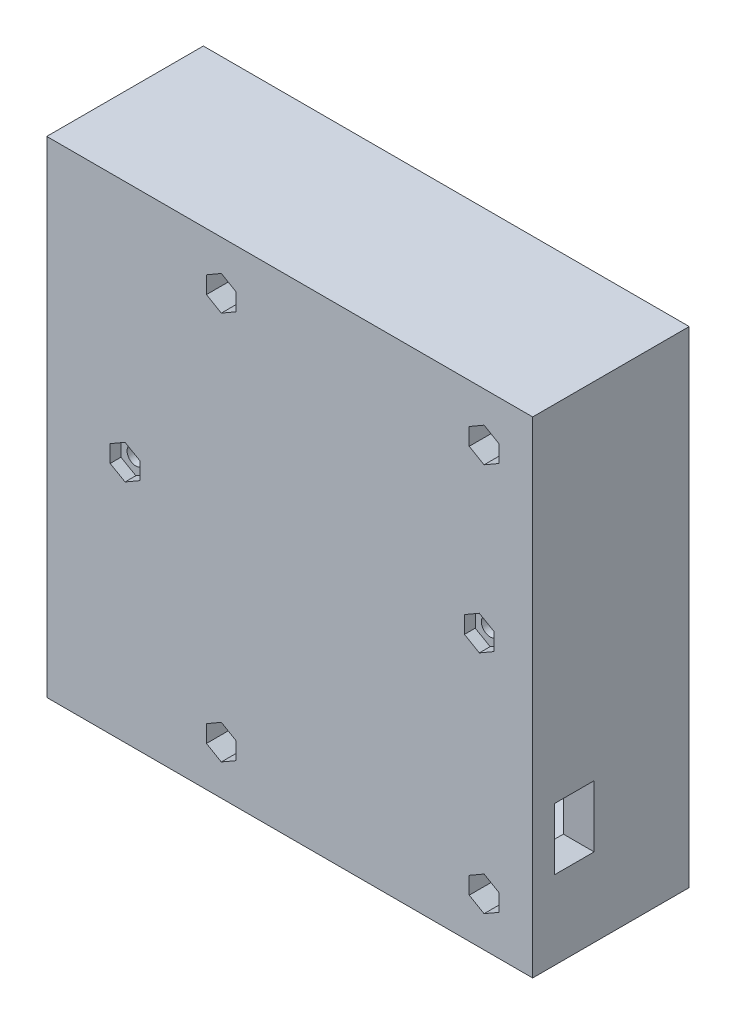
SolidWorks part; units mm, degrees
ref_plane "Alzado" through (0, 0, 0) normal (0, 0, 1) x (1, 0, 0)
ref_plane "Planta" through (0, 0, 0) normal (0, 1, 0) x (1, 0, 0)
ref_plane "Vista lateral" through (0, 0, 0) normal (1, 0, 0) x (0, 0, -1)
sketch "Croquis1" plane through (0, 0, 0) normal (0, 0, 1) x (1, 0, 0)
  line L0 (-44.4885, -46.7117) -> (45.5115, -46.7117)
  line L1 (45.5115, -46.7117) -> (45.5115, 43.2883)
  line L2 (34.2095, -31.6555) -> (34.2095, -33.0328) construction
  line L4 (-43.9885, 43.2883) -> (-45.9617, 43.2883) construction
  line L5 (-44.4885, 42.7883) -> (-44.4885, 44.5722) construction
  line L6 (-44.4885, 43.2883) -> (-44.4885, -46.7117)
  line L7 (-44.4885, 43.2883) -> (45.5115, 43.2883)
  dimension "D1" = 34.2095
  dimension "D2" = 45.5115
extrude "Saliente-Extruir1" add sketch "Croquis1" along normal blind 4
sketch "Croquis2" plane through (0, 0, 0) normal (0, 0, -1) x (-1, 0, 0)
  line L0 (-19.2301, 43.2883) -> (-19.2301, 39.2883) construction
  line L1 (-45.5115, 43.2883) -> (44.4885, 43.2883) construction
  line L2 (-45.5115, 28.7784) -> (-41.5115, 28.7784) construction
  line L3 (-45.5115, -46.7117) -> (-45.5115, 43.2883) construction
  line L4 (-24.9283, -46.7117) -> (-24.9283, -42.7117) construction
  line L5 (44.4885, -46.7117) -> (-45.5115, -46.7117) construction
  line L6 (44.4885, -27.1574) -> (40.4885, -27.1574) construction
  line L7 (44.4885, 43.2883) -> (44.4885, -46.7117) construction
  line L8 (40.4885, -27.1574) -> (40.4885, -42.7117)
  line L9 (40.4885, -42.7117) -> (-41.5115, -42.7117)
  line L10 (-41.5115, -42.7117) -> (-41.5115, 39.2883)
  line L11 (-41.5115, 39.2883) -> (40.4885, 39.2883)
  line L12 (40.4885, 39.2883) -> (40.4885, -27.1574)
  line L14 (-45.5115, 43.2883) -> (44.4885, 43.2883)
  line L15 (-45.5115, 43.2883) -> (-45.5115, -46.7117)
  line L16 (-45.5115, -46.7117) -> (44.4885, -46.7117)
  line L17 (44.4885, 43.2883) -> (44.4885, -46.7117)
  dimension "D1" = 4
  dimension "D2" = 20.5832
  dimension "D3" = 26.2813
  dimension "D4" = 19.5543
  dimension "D5" = 75.4901
extrude "Saliente-Extruir2" add sketch "Croquis2" along normal blind 25
sketch "Croquis4" plane through (45.5115, 0, 0) normal (1, 0, 0) x (0, 0, -1)
  line L0 (2.411, -26.4653) -> (-4, -26.4653) construction
  line L1 (0, -21.4747) -> (0, -31.4518)
  line L5 (0, -31.4518) -> (0, -32.1752)
  line L6 (0, -32.1752) -> (7.3834, -32.1752)
  line L13 (7.3834, -32.1752) -> (7.3834, -31.4518)
  line L14 (-4, -25.6688) -> (0, -25.6688) construction
  line L15 (7.3834, -21.4747) -> (7.3834, -20.7513)
  line L16 (7.3834, -21.4747) -> (7.3834, -31.4518)
  line L18 (7.3834, -20.7513) -> (0, -20.7513)
  line L19 (0, -20.7513) -> (0, -21.4747)
extrude "Cortar-Extruir1" cut sketch "Croquis4" against normal blind 4 draft 23
sketch "Croquis6" plane through (0, 0, 0) normal (0, 0, -1) x (-1, 0, 0)
  line L0 (-41.5115, 39.2883) -> (-41.5115, -42.7117) construction
  line L1 (-41.5115, 39.2883) -> (-31.5115, 39.2883)
  line L2 (-41.5115, 39.2883) -> (-41.5115, 29.2883)
  line L3 (-41.5115, 29.2883) -> (-31.5115, 29.2883)
  line L4 (-31.5115, 39.2883) -> (-31.5115, 29.2883)
  line L5 (40.4885, 39.2883) -> (-41.5115, 39.2883) construction
  line L6 (-41.5115, -42.7117) -> (40.4885, -42.7117) construction
  line L7 (-41.5115, -42.7117) -> (-31.5115, -42.7117)
  line L8 (-41.5115, -42.7117) -> (-41.5115, -32.7117)
  line L9 (-41.5115, -32.7117) -> (-31.5115, -32.7117)
  line L10 (-31.5115, -42.7117) -> (-31.5115, -32.7117)
  line L11 (-41.5115, 39.2883) -> (-41.5115, -42.7117) construction
  line L12 (40.4885, 39.2883) -> (-41.5115, 39.2883) construction
  line L14 (17.1571, -42.7117) -> (7.1571, -42.7117)
  line L15 (17.1571, -42.7117) -> (17.1571, -32.7117)
  line L16 (17.1571, -32.7117) -> (7.1571, -32.7117)
  line L17 (7.1571, -42.7117) -> (7.1571, -32.7117)
  line L18 (17.1571, 39.2883) -> (7.1571, 39.2883)
  line L19 (17.1571, 39.2883) -> (17.1571, 29.2883)
  line L20 (17.1571, 29.2883) -> (7.1571, 29.2883)
  line L21 (7.1571, 39.2883) -> (7.1571, 29.2883)
  dimension "D1" = 10
  dimension "D2" = 48.6686
extrude "Saliente-Extruir4" add sketch "Croquis6" along normal blind 4
sketch "Croquis7" plane through (0, 0, -4) normal (0, 0, -1) x (-1, 0, 0)
  line L0 (-36.5115, -32.7117) -> (-36.5115, -42.7117) construction
  line L1 (-31.5115, -32.7117) -> (-41.5115, -32.7117) construction
  line L2 (-41.5115, -42.7117) -> (40.4885, -42.7117) construction
  line L3 (-36.5115, 29.2883) -> (-36.5115, 39.2883) construction
  line L4 (-41.5115, 29.2883) -> (-31.5115, 29.2883) construction
  line L5 (40.4885, 39.2883) -> (-41.5115, 39.2883) construction
  line L6 (-31.5115, 34.2883) -> (-41.5115, 34.2883) construction
  line L7 (-31.5115, 29.2883) -> (-31.5115, 39.2883) construction
  line L8 (-41.5115, 39.2883) -> (-41.5115, -42.7117) construction
  line L9 (-31.5115, -37.7117) -> (-41.5115, -37.7117) construction
  line L10 (-31.5115, -42.7117) -> (-31.5115, -32.7117) construction
  line L12 (12.1571, -32.7117) -> (12.1571, -42.7117) construction
  line L13 (17.1571, -32.7117) -> (7.1571, -32.7117) construction
  line L14 (12.1571, 29.2883) -> (12.1571, 39.2883) construction
  line L15 (7.1571, 29.2883) -> (17.1571, 29.2883) construction
  line L16 (-41.5115, 39.2883) -> (-41.5115, 29.2883) construction
  circle A0 centre (-36.5115, 34.2883) radius 1.625
  circle A1 centre (-36.5115, -37.7117) radius 1.625
  circle A2 centre (12.1571, -37.7117) radius 1.625
  circle A3 centre (12.1571, 34.2883) radius 1.625
  dimension "D1" = 3.25
extrude "Cortar-Extruir2" cut sketch "Croquis7" against normal up to vertex (8 mm away) up to point (-44.4885, 43.2883, 4)
sketch "Croquis8" plane through (0, 0, 4) normal (0, 0, 1) x (1, 0, 0)
  line L0 (45.5115, -46.7117) -> (45.5115, 43.2883) construction
  line L1 (36.5115, -40.8917) -> (39.2654, -39.3017)
  line L2 (39.2654, -39.3017) -> (39.2654, -36.1217)
  line L3 (39.2654, -36.1217) -> (36.5115, -34.5317)
  line L4 (36.5115, -34.5317) -> (33.7575, -36.1217)
  line L5 (33.7575, -36.1217) -> (33.7575, -39.3017)
  line L6 (33.7575, -39.3017) -> (36.5115, -40.8917)
  line L7 (36.5115, 31.1083) -> (39.2654, 32.6983)
  line L8 (39.2654, 32.6983) -> (39.2654, 35.8783)
  line L9 (39.2654, 35.8783) -> (36.5115, 37.4683)
  line L10 (36.5115, 37.4683) -> (33.7575, 35.8783)
  line L11 (33.7575, 35.8783) -> (33.7575, 32.6983)
  line L12 (33.7575, 32.6983) -> (36.5115, 31.1083)
  circle A0 centre (36.5115, -37.7117) radius 2.754 construction
  circle A1 centre (36.5115, 34.2883) radius 2.754 construction
  dimension "D1" = 5.5079
  dimension "D2" = 6.246
  dimension "D3" = 5.82
  dimension "D4" = 77.82
extrude "Cortar-Extruir3" cut sketch "Croquis8" against normal blind 6
sketch "Croquis9" plane through (0, 0, 0) normal (0, 0, -1) x (-1, 0, 0)
  line L0 (40.4885, -42.7117) -> (40.4885, 39.2883) construction
  line L1 (-31.5115, -42.7117) -> (7.1571, -42.7117) construction
  circle A0 centre (-35.6315, 3.6783) radius 1.625
  circle A1 centre (29.9885, -1.7117) radius 1.625
  dimension "D1" = 3.25
  dimension "D2" = 10.5
  dimension "D3" = 76.12
  dimension "D4" = 41
  dimension "D5" = 46.39
extrude "Cortar-Extruir4" cut sketch "Croquis9" against normal up to vertex (4 mm away) up to point (-44.4885, 43.2883, 4)
sketch "Croquis10" plane through (0, 0, 4) normal (0, 0, 1) x (1, 0, 0)
  line L0 (39.2654, -39.3017) -> (39.2654, -36.1217) construction
  line L1 (-29.9885, -4.8917) -> (-27.2346, -3.3017)
  line L2 (-27.2346, -3.3017) -> (-27.2346, -0.1217)
  line L3 (-27.2346, -0.1217) -> (-29.9885, 1.4683)
  line L4 (-29.9885, 1.4683) -> (-32.7425, -0.1217)
  line L5 (-32.7425, -0.1217) -> (-32.7425, -3.3017)
  line L6 (-32.7425, -3.3017) -> (-29.9885, -4.8917)
  line L7 (35.6315, 0.4983) -> (38.3854, 2.0883)
  line L8 (38.3854, 2.0883) -> (38.3854, 5.2683)
  line L9 (38.3854, 5.2683) -> (35.6315, 6.8583)
  line L10 (35.6315, 6.8583) -> (32.8775, 5.2683)
  line L11 (32.8775, 5.2683) -> (32.8775, 2.0883)
  line L12 (32.8775, 2.0883) -> (35.6315, 0.4983)
  circle A0 centre (-29.9885, -1.7117) radius 2.754 construction
  circle A1 centre (35.6315, 3.6783) radius 2.754 construction
  point P9 (35.6315, 3.6783)
  point P17 (-29.9885, -1.7117)
  point P18 (-29.9885, -1.7117)
  dimension "D1" = 5.5079
  dimension "D2" = 0.88
  dimension "D3" = 66.5
  dimension "D4" = 36
  dimension "D5" = 41.39
extrude "Cortar-Extruir5" cut sketch "Croquis10" against normal blind 2
sketch "Croquis11" plane through (0, 0, 4) normal (0, 0, 1) x (1, 0, 0)
  line L0 (-32.7425, -0.1217) -> (-32.7425, -3.3017) construction
  line L1 (-12.1571, 31.1083) -> (-9.4031, 32.6983)
  line L2 (-9.4031, 32.6983) -> (-9.4031, 35.8783)
  line L3 (-9.4031, 35.8783) -> (-12.1571, 37.4683)
  line L4 (-12.1571, 37.4683) -> (-14.9111, 35.8783)
  line L5 (-14.9111, 35.8783) -> (-14.9111, 32.6983)
  line L6 (-14.9111, 32.6983) -> (-12.1571, 31.1083)
  line L7 (-12.1571, -34.5317) -> (-14.9111, -36.1217)
  line L8 (-14.9111, -36.1217) -> (-14.9111, -39.3017)
  line L9 (-14.9111, -39.3017) -> (-12.1571, -40.8917)
  line L10 (-12.1571, -40.8917) -> (-9.4031, -39.3017)
  line L11 (-9.4031, -39.3017) -> (-9.4031, -36.1217)
  line L12 (-9.4031, -36.1217) -> (-12.1571, -34.5317)
  circle A0 centre (-12.1571, 34.2883) radius 2.754 construction
  circle A1 centre (-12.1571, -37.7117) radius 2.754 construction
  point P9 (0, 0)
  point P17 (-12.1571, -37.7117)
  point P18 (-12.1571, 34.2883)
  dimension "D1" = 5.5079
  dimension "D2" = 17.8314
  dimension "D3" = 72
extrude "Cortar-Extruir6" cut sketch "Croquis11" against normal blind 6
